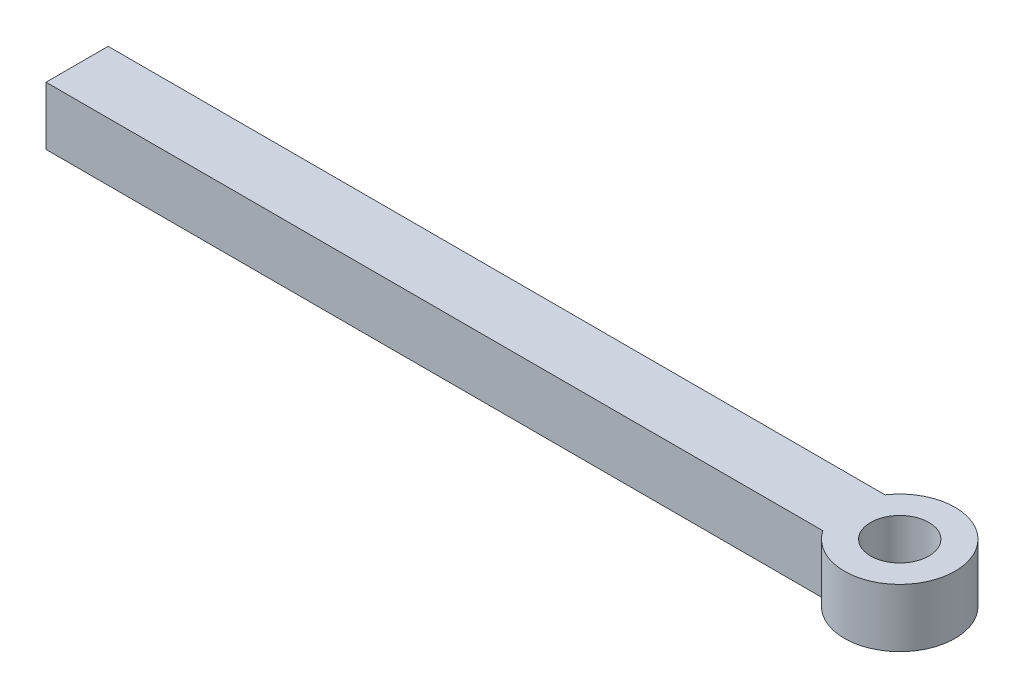
SolidWorks part; units mm, degrees
ref_plane "Plano frontal" through (0, 0, 0) normal (0, 0, 1) x (1, 0, 0)
ref_plane "Plano superior" through (0, 0, 0) normal (0, 1, 0) x (1, 0, 0)
ref_plane "Plano direito" through (0, 0, 0) normal (1, 0, 0) x (0, 0, -1)
sketch "Esboço1" plane through (0, 0, 0) normal (0, 1, 0) x (1, 0, 0)
  line L2 (0, 16) -> (200, 16)
  line L3 (0, 0) -> (200, 0)
  line L4 (0, 16) -> (0, 0)
  line L8 (111.7925, 14.4945) -> (111.7925, -12.8649) construction
  arc A5 (200, 0) -> (200, 16) centre (211.7925, 8) ccw
  point P0 (0, 0)
  dimension "D1" = 16
  dimension "D2" = 211.7925
  dimension "D3" = 28.5
  dimension "D4" = 200
extrude "Ressalto-extrusão1" add sketch "Esboço1" along normal blind 15
sketch "Esboço3" plane through (0, 15, 0) normal (0, 1, 0) x (1, 0, 0)
  line L0 (211.3515, 0) -> (233.8296, 0) construction
  circle A1 centre (211.7925, 8) radius 7.5
  dimension "D1" = 15
extrude "Corte-extrusão2" cut sketch "Esboço3" against normal through all
sketch "Esboço4" plane through (0, 0, 0) normal (-1, 0, 0) x (0, 0, 1)
  line L0 (-16, 0) -> (0, 0) construction
  line L1 (0, 15) -> (0, 0) construction
  circle A0 centre (-8, 7.5) radius 4
  dimension "D1" = 8
  dimension "D2" = 7.5
  dimension "D3" = 8
extrude "Corte-extrusão3" cut sketch "Esboço4" against normal blind 30
